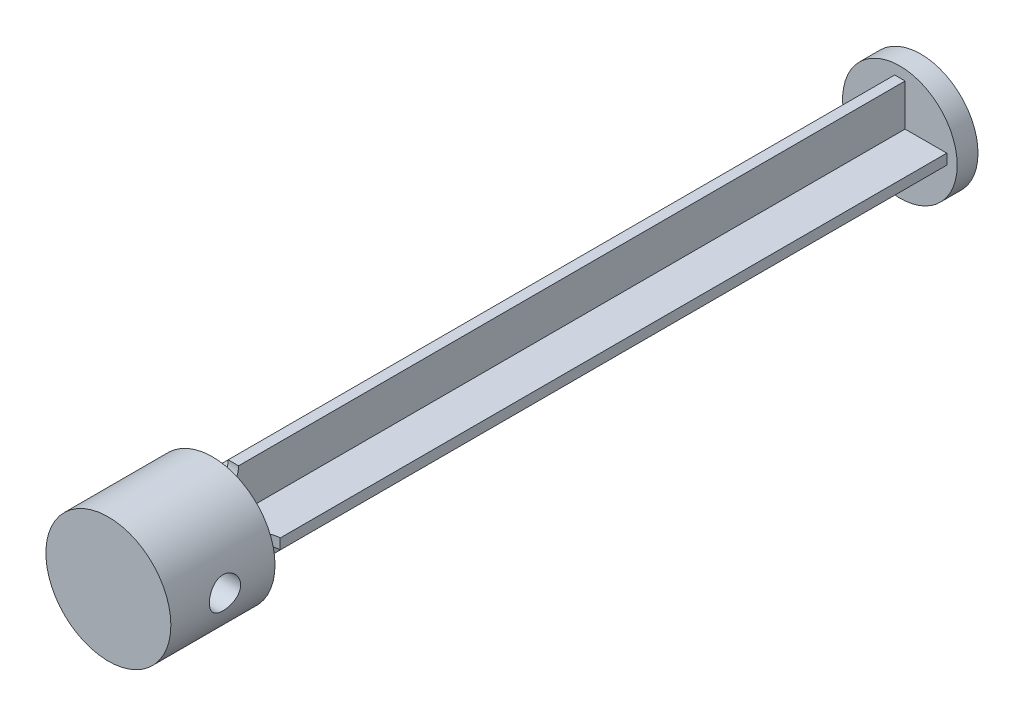
SolidWorks part; units mm, degrees
ref_plane "Front" through (0, 0, 0) normal (0, 0, 1) x (1, 0, 0)
ref_plane "Top" through (0, 0, 0) normal (0, 1, 0) x (1, 0, 0)
ref_plane "Right" through (0, 0, 0) normal (1, 0, 0) x (0, 0, -1)
sketch "Sketch1" plane through (0, 0, 0) normal (0, 0, 1) x (1, 0, 0)
  circle A0 centre (0, 0) radius 6.985
  dimension "D1" = 13.97
extrude "Boss-Extrude1" add sketch "Sketch1" along normal blind 2.54
sketch "Sketch2" plane through (0, 0, 2.54) normal (0, 0, 1) x (1, 0, 0)
  line L0 (-0.635, 0.635) -> (-0.635, -0.635) construction
  line L1 (-0.635, -0.635) -> (-5.715, -0.635)
  line L3 (-0.635, 0.635) -> (-5.715, 0.635)
  line L4 (-5.715, -0.635) -> (-5.715, 0.635)
  line L6 (-0.635, 0.635) -> (-0.635, 5.715)
  line L7 (-0.635, 5.715) -> (0.635, 5.715)
  line L8 (0.635, 0.635) -> (0.635, 5.715)
  line L9 (0.635, -0.635) -> (5.715, -0.635)
  line L11 (0.635, 0.635) -> (5.715, 0.635)
  line L12 (5.715, -0.635) -> (5.715, 0.635)
  line L14 (0.635, -0.635) -> (0.635, -5.715)
  line L15 (0.635, -5.715) -> (-0.635, -5.715)
  line L16 (-0.635, -0.635) -> (-0.635, -5.715)
  line L17 (-0.635, 0.635) -> (0.635, 0.635) construction
  point P2 (-0.635, 0)
  point P13 (0, 0.635)
  point P14 (0, 0)
  dimension "D1" = 5.08
  dimension "D2" = 1.27
extrude "Boss-Extrude2" add sketch "Sketch2" along normal blind 81.28
sketch "Sketch3" plane through (0, 0, 83.82) normal (0, 0, 1) x (1, 0, 0)
  line L1 (-3.175, 0.635) -> (-0.635, 0.635)
  line L2 (-3.175, 0.635) -> (-3.175, -0.635)
  line L3 (-3.175, -0.635) -> (-0.635, -0.635)
  line L5 (-0.635, 3.175) -> (0.635, 3.175)
  line L6 (-0.635, 3.175) -> (-0.635, 0.635)
  line L8 (0.635, 3.175) -> (0.635, 0.635)
  line L9 (3.175, 0.635) -> (0.635, 0.635)
  line L10 (3.175, 0.635) -> (3.175, -0.635)
  line L11 (3.175, -0.635) -> (0.635, -0.635)
  line L14 (0.635, -0.635) -> (5.715, -0.635) construction
  line L15 (0.635, -3.175) -> (-0.635, -3.175)
  line L16 (0.635, -3.175) -> (0.635, -0.635)
  line L18 (-0.635, -3.175) -> (-0.635, -0.635)
  line L19 (0.635, 5.715) -> (-0.635, 5.715) construction
  line L20 (5.715, -0.635) -> (5.715, 0.635) construction
  line L21 (-5.715, 0.635) -> (-5.715, -0.635) construction
  line L22 (-0.635, -5.715) -> (0.635, -5.715) construction
  line L23 (-0.635, 0.635) -> (-5.715, 0.635) construction
  line L24 (-0.635, 5.715) -> (-0.635, 0.635) construction
  dimension "D1" = 2.54
  dimension "D2" = 2.54
  dimension "D3" = 2.54
  dimension "D4" = 2.54
extrude "Boss-Extrude3" add sketch "Sketch3" along normal blind 2.54
fillet "Fillet1" radius 2.54 4 edges at (0, -3.175, 83.82) (3.175, 0, 83.82) (0, 3.175, 83.82) (-3.175, 0, 83.82)
sketch "Sketch4" plane through (0, 0, 86.36) normal (0, 0, 1) x (1, 0, 0)
  circle A0 centre (0, 0) radius 7.62
  dimension "D1" = 15.24
extrude "Boss-Extrude4" add sketch "Sketch4" along normal blind 12.7
sketch "Sketch5" plane through (5.715, 0, 0) normal (1, 0, 0) x (0, 0, -1)
  line L0 (-83.82, -0.635) -> (-83.82, 0.635) construction
  circle A0 centre (-92.4585, 0) radius 1.905
  point P2 (0, 0)
  point P3 (-83.82, 0)
  dimension "D1" = 3.81
extrude "Cut-Extrude1" cut sketch "Sketch5" against normal through all both and the other way through all
equation "\"D2@Sketch3\"=\"D1@Sketch3\""
equation "\"D3@Sketch3\"=\"D1@Sketch3\""
equation "\"D4@Sketch3\"=\"D1@Sketch3\""
